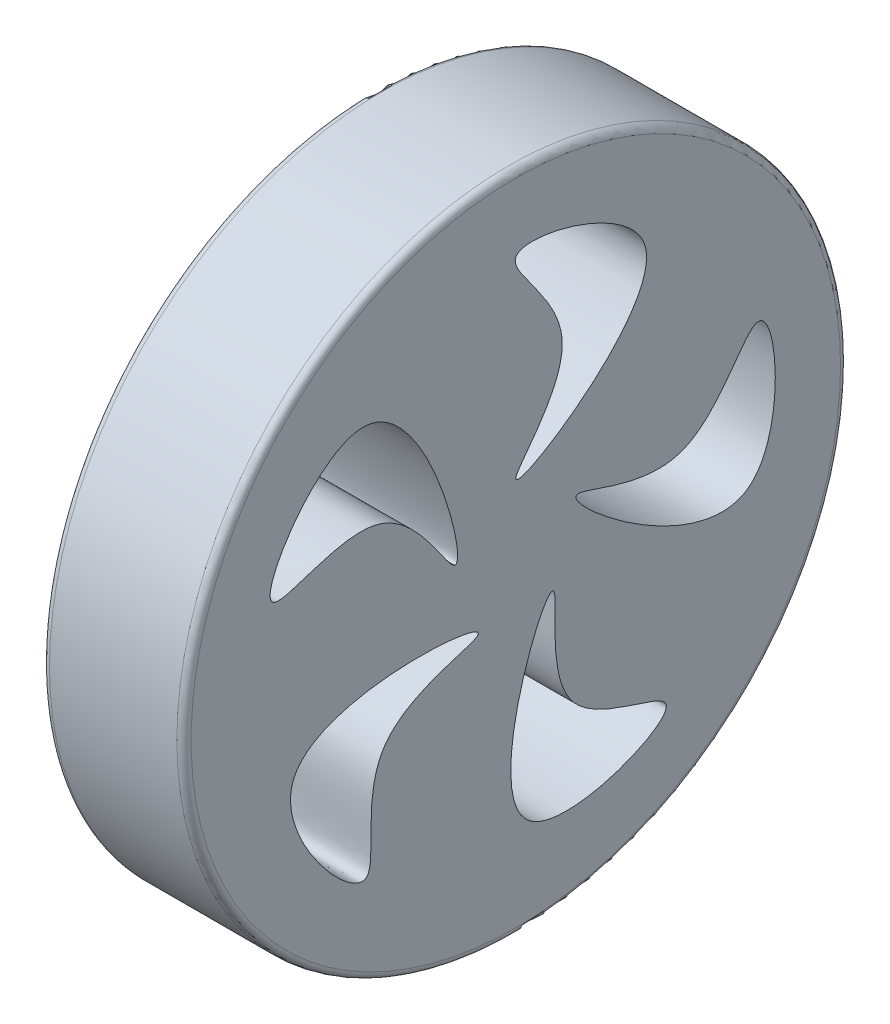
SolidWorks part; units mm, degrees
material "NEOPRENE"
ref_plane "Front Plane" through (0, 0, 0) normal (0, 0, 1) x (1, 0, 0)
ref_plane "Top Plane" through (0, 0, 0) normal (0, 1, 0) x (1, 0, 0)
ref_plane "Right Plane" through (0, 0, 0) normal (1, 0, 0) x (0, 0, -1)
sketch "Sketch1" plane through (0, 0, 0) normal (1, 0, 0) x (0, 0, -1)
  circle A0 centre (0, 0) radius 46.88
  dimension "D1" = 93.76
extrude "Boss-Extrude1" add sketch "Sketch1" along normal blind 20
sketch "Sketch3" plane through (20, 0, 0) normal (1, 0, 0) x (0, 0, -1)
  spline S0 degree 3 poles (36.5513, 29.758) (-11.8834, -0.6084) (13.531, 22.8824) (-10.3804, 41.627) (36.5513, 29.758) (-11.8834, -0.6084) (13.531, 22.8824) knots -0.805035 -0.606981 -0.348478 0 0.194965 0.393019 0.651522 1 1.194965 1.393019 1.651522 only from (0, 9.1193) to (0, 9.1193)
  spline S1 degree 3 poles (39.5965, -25.5666) (-4.2508, 11.1138) (25.9437, -5.7977) (36.3819, 22.7358) (39.5965, -25.5666) (-4.2508, 11.1138) (25.9437, -5.7977) knots -0.805035 -0.606981 -0.348478 0 0.194965 0.393019 0.651522 1 1.194965 1.393019 1.651522 only from (8.673, 2.818) to (8.673, 2.818)
  spline S2 degree 3 poles (-12.0793, -45.559) (9.2562, 7.4771) (2.5031, -26.4655) (32.8656, -27.5755) (-12.0793, -45.559) (9.2562, 7.4771) (2.5031, -26.4655) knots -0.805035 -0.606981 -0.348478 0 0.194965 0.393019 0.651522 1 1.194965 1.393019 1.651522 only from (5.3602, -7.3777) to (5.3602, -7.3777)
  spline S3 degree 3 poles (-47.0619, -2.5904) (9.9715, -6.4927) (-24.3967, -10.5589) (-16.0699, -39.7784) (-47.0619, -2.5904) (9.9715, -6.4927) (-24.3967, -10.5589) knots -0.805035 -0.606981 -0.348478 0 0.194965 0.393019 0.651522 1 1.194965 1.393019 1.651522 only from (-5.3602, -7.3777) to (-5.3602, -7.3777)
  spline S4 degree 3 poles (-17.0065, 43.9581) (-3.0935, -11.4898) (-17.5811, 19.9398) (-42.7974, 2.9911) (-17.0065, 43.9581) (-3.0935, -11.4898) (-17.5811, 19.9398) knots -0.805035 -0.606981 -0.348478 0 0.194965 0.393019 0.651522 1 1.194965 1.393019 1.651522 only from (-8.673, 2.818) to (-8.673, 2.818)
  point P23 (0, 0)
  dimension "D1" = 80.8452
  dimension "D5" = 11.678
  dimension "D2" = 22.5031
  dimension "D3" = 36.1493
  dimension "D4" = 28.5389
  dimension "D6" = 15.1414
extrude "Cut-Extrude1" cut sketch "Sketch3" against normal up to next
ref_axis "Axis1" through (20, 0, 0) along (-1, 0, 0)
ref_plane "Plane1" through (10, 0, 0) normal (-1, 0, 0) x (0, 0, 1)
ref_point "Point1"
fillet "Fillet2" radius 1 2 edges at (0, 0, -46.88) (20, 0, -46.88)
